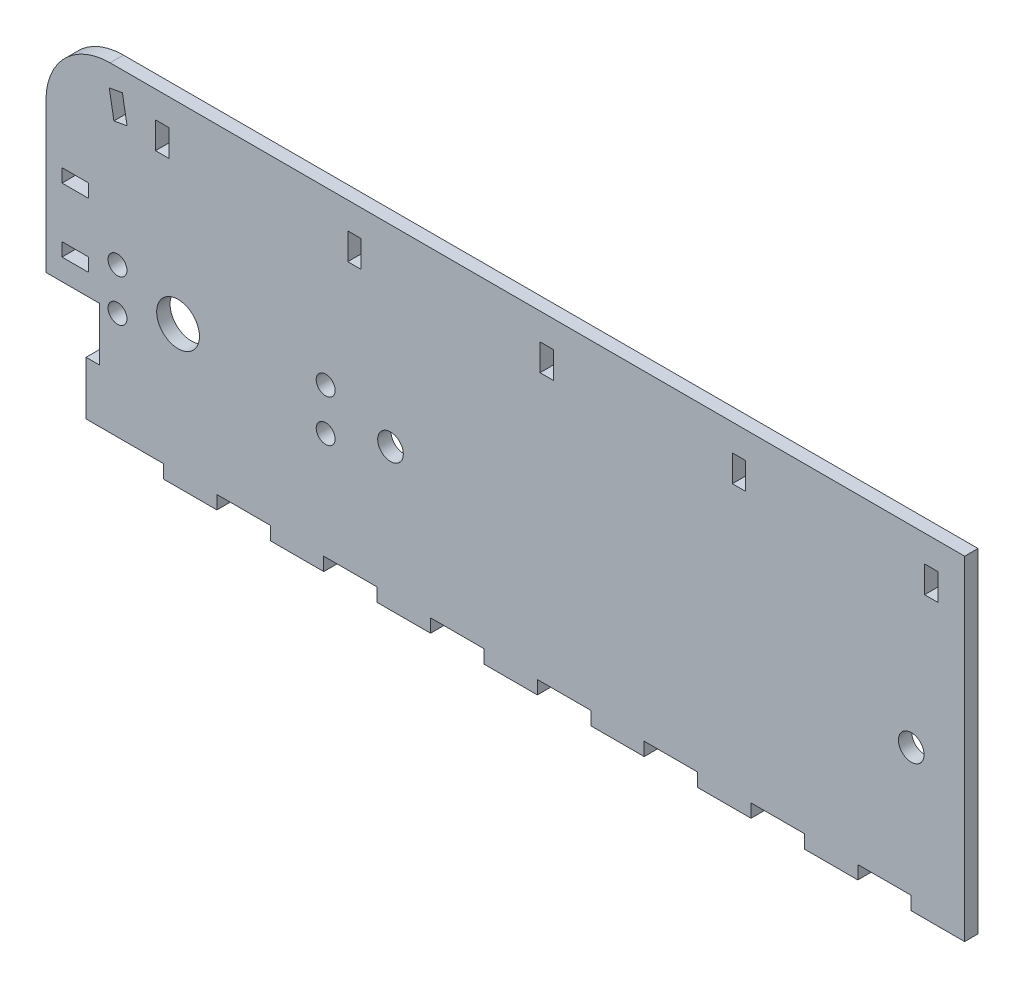
SolidWorks part; units mm, degrees
ref_plane "Front" through (0, 0, 0) normal (0, 0, 1) x (1, 0, 0)
ref_plane "Top" through (0, 0, 0) normal (0, 1, 0) x (1, 0, 0)
ref_plane "Right" through (0, 0, 0) normal (1, 0, 0) x (0, 0, -1)
sketch "Sketch1" plane through (0, 0, 0) normal (0, 0, 1) x (1, 0, 0)
  line L5 (0, 0) -> (228.6, 0)
  line L6 (0, 0) -> (0, 76.2)
  line L7 (0, 76.2) -> (228.6, 76.2)
  line L8 (228.6, 0) -> (228.6, 76.2)
  circle A0 centre (215.9, 30.48) radius 3.048
  circle A1 centre (92.075, 30.48) radius 3.048
  circle A2 centre (41.5608, 30.48) radius 5.08
  dimension "D7" = 6.096
  dimension "D8" = 6.096
  dimension "D9" = 10.16
  dimension "D1" = 228.6
  dimension "D2" = 76.2
  dimension "D3" = 50.5142
  dimension "D4" = 123.825
  dimension "D5" = 30.48
  dimension "D6" = 12.7
extrude "Boss-Extrude1" add sketch "Sketch1" along normal blind 3.175
sketch "Sketch2" plane through (0, 0, 0) normal (0, -1, 0) x (1, 0, 0)
  line L0 (0, 3.175) -> (228.6, 3.175) construction
  line L1 (228.6, 0) -> (215.9, 0)
  line L2 (228.6, 0) -> (228.6, 3.175)
  line L3 (228.6, 3.175) -> (215.9, 3.175)
  line L4 (215.9, 0) -> (215.9, 3.175)
  line L5 (203.2, 0) -> (203.2, 3.175)
  line L6 (203.2, 0) -> (190.5, 0)
  line L7 (190.5, 0) -> (190.5, 3.175)
  line L8 (203.2, 3.175) -> (190.5, 3.175)
  line L9 (177.8, 0) -> (177.8, 3.175)
  line L10 (177.8, 0) -> (165.1, 0)
  line L11 (165.1, 0) -> (165.1, 3.175)
  line L12 (177.8, 3.175) -> (165.1, 3.175)
  line L13 (152.4, 0) -> (152.4, 3.175)
  line L14 (152.4, 0) -> (139.7, 0)
  line L15 (139.7, 0) -> (139.7, 3.175)
  line L16 (152.4, 3.175) -> (139.7, 3.175)
  line L17 (127, 0) -> (127, 3.175)
  line L18 (127, 0) -> (114.3, 0)
  line L19 (114.3, 0) -> (114.3, 3.175)
  line L20 (127, 3.175) -> (114.3, 3.175)
  line L21 (101.6, 0) -> (101.6, 3.175)
  line L22 (101.6, 0) -> (88.9, 0)
  line L23 (88.9, 0) -> (88.9, 3.175)
  line L24 (101.6, 3.175) -> (88.9, 3.175)
  line L25 (76.2, 0) -> (76.2, 3.175)
  line L26 (76.2, 0) -> (63.5, 0)
  line L27 (63.5, 0) -> (63.5, 3.175)
  line L28 (76.2, 3.175) -> (63.5, 3.175)
  line L29 (50.8, 0) -> (50.8, 3.175)
  line L30 (50.8, 0) -> (38.1, 0)
  line L31 (38.1, 0) -> (38.1, 3.175)
  line L32 (50.8, 3.175) -> (38.1, 3.175)
  dimension "D1" = 12.7
  dimension "D2" = 8
extrude "Boss-Extrude2" add sketch "Sketch2" along normal blind 3.175
sketch "Sketch3" plane through (0, 0, 0) normal (0, 0, -1) x (-1, 0, 0)
  line L1 (0, 0) -> (-22.86, 0)
  line L2 (0, 0) -> (0, 25.4)
  line L3 (0, 25.4) -> (-22.86, 25.4)
  line L4 (-22.86, 0) -> (-22.86, 25.4)
  dimension "D1" = 25.4
  dimension "D2" = 22.86
extrude "Cut-Extrude1" cut sketch "Sketch3" against normal through all
sketch "Sketch4" plane through (22.86, 0, 0) normal (-1, 0, 0) x (0, 0, 1)
  line L0 (3.175, 25.4) -> (3.175, 0) construction
  line L1 (0, 0) -> (3.175, 0)
  line L2 (0, 0) -> (0, 12.7)
  line L3 (0, 12.7) -> (3.175, 12.7)
  line L4 (3.175, 0) -> (3.175, 12.7)
  dimension "D1" = 12.7
extrude "Boss-Extrude3" add sketch "Sketch4" along normal blind 3.175
sketch "Sketch6" plane through (0, 0, 0) normal (0, 0, -1) x (-1, 0, 0)
  circle A0 centre (-27.1608, 35.48) radius 2.25
  circle A1 centre (-27.1608, 25.48) radius 2.25
  circle A2 centre (-76.6608, 35.48) radius 2.25
  circle A3 centre (-76.6608, 25.48) radius 2.25
extrude "Cut-Extrude2" cut sketch "Sketch6" against normal through all
sketch "Sketch8" plane through (0, 0, 3.175) normal (0, 0, 1) x (1, 0, 0)
  line L8 (0, 76.2) -> (10.16, 76.2)
  line L9 (0, 76.2) -> (0, 25.4)
  line L10 (0, 25.4) -> (10.16, 25.4)
  line L11 (10.16, 76.2) -> (10.16, 25.4)
  line L12 (0, 25.4) -> (22.86, 25.4) construction
  line L13 (22.86, 25.4) -> (22.86, 12.7) construction
  dimension "D1" = 12.7
extrude "Cut-Extrude3" cut sketch "Sketch8" against normal through all
sketch "Sketch12" plane through (0, 0, 0) normal (0, 0, -1) x (-1, 0, 0)
  line L0 (-164.0363, 64) -> (-164.0363, 1) construction
  line L1 (-139.0363, 1) -> (-139.0363, 64) construction
  line L2 (-140.0363, 65) -> (-163.0363, 65) construction
  line L3 (-164.0363, 64) -> (-164.0363, 1) construction
  line L4 (-139.0363, 1) -> (-139.0363, 64) construction
  line L5 (-140.0363, 65) -> (-163.0363, 65) construction
  line L6 (-228.6, 76.2) -> (-10.16, 76.2) construction
  line L7 (-222.25, 69.85) -> (-219.075, 69.85)
  line L8 (-222.25, 69.85) -> (-222.25, 63.5)
  line L9 (-222.25, 63.5) -> (-219.075, 63.5)
  line L10 (-219.075, 69.85) -> (-219.075, 63.5)
  line L11 (-228.6, -3.175) -> (-228.6, 76.2) construction
  line L12 (-176.53, 69.85) -> (-176.53, 63.5)
  line L13 (-176.53, 69.85) -> (-173.355, 69.85)
  line L14 (-173.355, 69.85) -> (-173.355, 63.5)
  line L15 (-176.53, 63.5) -> (-173.355, 63.5)
  line L16 (-130.81, 69.85) -> (-130.81, 63.5)
  line L17 (-130.81, 69.85) -> (-127.635, 69.85)
  line L18 (-127.635, 69.85) -> (-127.635, 63.5)
  line L19 (-130.81, 63.5) -> (-127.635, 63.5)
  line L20 (-85.09, 69.85) -> (-85.09, 63.5)
  line L21 (-85.09, 69.85) -> (-81.915, 69.85)
  line L22 (-81.915, 69.85) -> (-81.915, 63.5)
  line L23 (-85.09, 63.5) -> (-81.915, 63.5)
  line L24 (-39.37, 69.85) -> (-39.37, 63.5)
  line L25 (-39.37, 69.85) -> (-36.195, 69.85)
  line L26 (-36.195, 69.85) -> (-36.195, 63.5)
  line L27 (-39.37, 63.5) -> (-36.195, 63.5)
  dimension "D1" = 6.35
  dimension "D2" = 3.175
  dimension "D3" = 6.35
  dimension "D4" = 6.35
  dimension "D5" = 5
extrude "Cut-Extrude5" cut sketch "Sketch12" against normal blind 3.175
sketch "Sketch13" plane through (0, 0, 3.175) normal (0, 0, 1) x (1, 0, 0)
  line L4 (25.4, 60.96) -> (9.8038, 76.5562) construction
  line L9 (10.16, 60.96) -> (10.16, 76.2)
  line L10 (10.16, 76.2) -> (25.4, 76.2)
  arc A0 (10.16, 60.96) -> (25.4, 76.2) centre (25.4, 60.96) cw
  point P10 (10.16, 76.2)
  dimension "D1" = 15.24
extrude "Cut-Extrude6" cut sketch "Sketch13" against normal through all
sketch "Sketch14" plane through (0, 0, 3.175) normal (0, 0, 1) x (1, 0, 0)
  line L0 (20.32, 25.4) -> (20.32, 75.3284) construction
  line L1 (10.16, 25.4) -> (22.86, 25.4) construction
  line L2 (20.32, 30.48) -> (13.97, 30.48)
  line L3 (20.32, 30.48) -> (20.32, 33.655)
  line L4 (20.32, 33.655) -> (13.97, 33.655)
  line L5 (13.97, 30.48) -> (13.97, 33.655)
  line L10 (20.32, 45.72) -> (20.32, 48.895)
  line L11 (20.32, 45.72) -> (13.97, 45.72)
  line L12 (13.97, 45.72) -> (13.97, 48.895)
  line L13 (20.32, 48.895) -> (13.97, 48.895)
  line L14 (22.86, 25.4) -> (22.86, 12.7) construction
  arc A0 (25.4, 76.2) -> (10.16, 60.96) centre (25.4, 60.96) ccw construction
  dimension "D1" = 3.175
  dimension "D2" = 5.08
  dimension "D3" = 6.35
  dimension "D5" = 2.54
  dimension "D4" = 2
extrude "Cut-Extrude7" cut sketch "Sketch14" against normal through all
sketch "Sketch15" plane through (0, 0, 3.175) normal (0, 0, 1) x (1, 0, 0)
  line L0 (10.16, 60.96) -> (228.6, 60.96) construction
  line L1 (228.6, -3.175) -> (228.6, 76.2) construction
  line L2 (28.575, 60.96) -> (23.4055, 90.2779) construction
  line L3 (36.195, 63.5) -> (36.195, 69.85) construction
  line L8 (26.3059, 64.6866) -> (25.2032, 70.9401)
  line L9 (25.2032, 70.9401) -> (28.33, 71.4915)
  line L10 (28.33, 71.4915) -> (29.4327, 65.2379)
  line L11 (29.4327, 65.2379) -> (26.3059, 64.6866)
  point P10 (28.7465, 60.96)
  dimension "D1" = 7.62
  dimension "D2" = 80
  dimension "D3" = 3.175
  dimension "D4" = 6.35
  dimension "D5" = 1.5875
  dimension "D6" = 4.064
extrude "Cut-Extrude8" cut sketch "Sketch15" against normal through all
